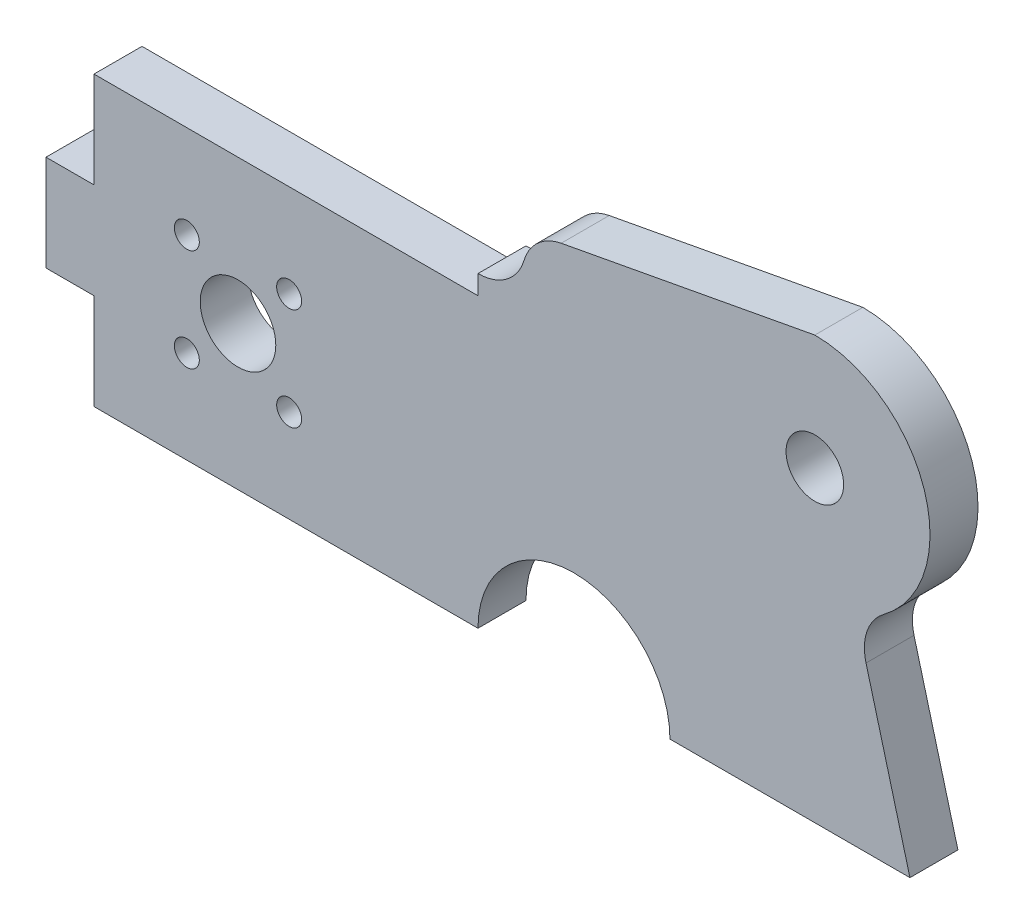
SolidWorks part; units mm, degrees
ref_plane "Front Plane" through (0, 0, 0) normal (0, 0, 1) x (1, 0, 0)
ref_plane "Top Plane" through (0, 0, 0) normal (0, 1, 0) x (1, 0, 0)
ref_plane "Right Plane" through (0, 0, 0) normal (1, 0, 0) x (0, 0, -1)
sketch "Sketch1" plane through (0, 0, 0) normal (0, 0, 1) x (1, 0, 0)
  line L0 (0, 0) -> (107.95, 0)
  line L3 (0, 38.1) -> (0, 25.4)
  line L4 (95.3675, 55.88) -> (0, 38.1)
  line L5 (0, 19.05) -> (100.2273, 19.05) construction
  line L6 (19.05, 19.05) -> (19.05, 28.62) construction
  line L7 (19.05, 19.05) -> (25.817, 25.817) construction
  line L8 (107.95, 0) -> (100.9363, 26.1756)
  line L10 (0, 12.7) -> (0, 0)
  line L11 (0, 25.4) -> (-6.35, 25.4)
  line L13 (0, 12.7) -> (-6.35, 12.7)
  line L14 (-6.35, 25.4) -> (-6.35, 12.7)
  line L15 (100.9363, 26.1756) -> (100.8688, 26.4276)
  arc A0 (100.8688, 26.4276) -> (95.3675, 55.88) centre (95.3675, 40.64) ccw
  circle A1 centre (95.3675, 40.64) radius 3.81
  circle A2 centre (19.05, 19.05) radius 9.57 construction
  circle A3 centre (25.817, 25.817) radius 1.651
  circle A4 centre (25.817, 12.283) radius 1.651
  circle A5 centre (12.283, 12.283) radius 1.651
  circle A6 centre (12.283, 25.817) radius 1.651
  point P26 (19.05, 19.05)
  dimension "D1" = 7.62
  dimension "D5" = 15.24
  dimension "D4" = 19.14
  dimension "D7" = 3.302
  dimension "D11" = 97.0107
  dimension "D2" = 38.1
  dimension "D3" = 40.64
  dimension "D6" = 107.95
  dimension "D8" = 45
  dimension "D9" = 4
  dimension "D10" = 19.05
  dimension "D12" = 75
  dimension "D14" = 12.7
  dimension "D15" = 12.7
  dimension "D16" = 6.35
extrude "Boss-Extrude1" add sketch "Sketch1" along normal blind 6.35
sketch "Sketch2" plane through (0, 0, 6.35) normal (0, 0, 1) x (1, 0, 0)
  circle A0 centre (95.3675, 40.64) radius 38.1 construction
sketch "Sketch3" plane through (0, 0, 0) normal (-1, 0, 0) x (0, 0, 1)
  line L0 (0, 38.1) -> (6.35, 25.4) construction
  line L1 (6.35, 12.7) -> (0, 0) construction
  circle A0 centre (3.175, 31.75) radius 1.5875
  circle A1 centre (3.175, 6.35) radius 1.5875
  dimension "D1" = 3.175
  dimension "D2" = 3.175
extrude "Cut-Extrude1" cut sketch "Sketch3" against normal blind 6.35
sketch "Sketch6" plane through (0, 0, 6.35) normal (0, 0, 1) x (1, 0, 0)
  line L0 (0, 0) -> (107.95, 0) construction
  line L1 (50.8, 0) -> (76.2, 0)
  arc A0 (76.2, 0) -> (50.8, 0) centre (63.5, 0) ccw
  dimension "D1" = 25.4
  dimension "D2" = 31.75
extrude "Cut-Extrude2" cut sketch "Sketch6" against normal blind 6.35
sketch "Sketch7" plane through (0, 0, 6.35) normal (0, 0, 1) x (1, 0, 0)
  line L0 (12.283, 25.817) -> (25.817, 12.283) construction
  line L1 (12.283, 12.283) -> (25.817, 25.817) construction
  circle A0 centre (19.05, 19.05) radius 5
  dimension "D1" = 10
extrude "Cut-Extrude3" cut sketch "Sketch7" against normal through all
fillet "Fillet1" radius 6.35 1 edges at (100.8688, 26.4276, 3.175)
sketch "Sketch8" plane through (0, 0, 6.35) normal (0, 0, 1) x (1, 0, 0)
  line L1 (0, 38.1) -> (50.8, 38.1)
  line L2 (0, 38.1) -> (0, 50.8)
  line L3 (0, 50.8) -> (50.8, 50.8)
  line L4 (50.8, 38.1) -> (50.8, 50.8)
  dimension "D1" = 50.8
  dimension "D2" = 12.7
extrude "Cut-Extrude4" cut sketch "Sketch8" against normal blind 50.8
sketch "Sketch9" plane through (0, 0, 6.35) normal (0, 0, 1) x (1, 0, 0)
  line L3 (50.8, 40.64) -> (57.15, 40.64)
  line L5 (57.15, 40.64) -> (50.8, 40.64)
  line L6 (57.15, 40.64) -> (57.15, 50.8)
  line L7 (57.15, 50.8) -> (50.8, 50.8)
  line L8 (50.8, 40.64) -> (50.8, 50.8)
  line L9 (0, 38.1) -> (50.8, 38.1) construction
  line M8 (50.8, 47.571) -> (50.8, 38.1)
  line M21 (95.3675, 55.88) -> (50.8, 47.571)
  dimension "D1" = 10.16
  dimension "D2" = 2.54
  dimension "D3" = 6.35
extrude "Cut-Extrude5" cut sketch "Sketch9" against normal blind 19.304 contours L3 L6 M21 M8 region at (54.0583, 44.4092, 6.35)
fillet "Fillet6" radius 6.35 1 edges at (57.15, 40.64, 3.175)
fillet "Fillet7" radius 6.35 1 edges at (57.15, 48.7549, 3.175)
